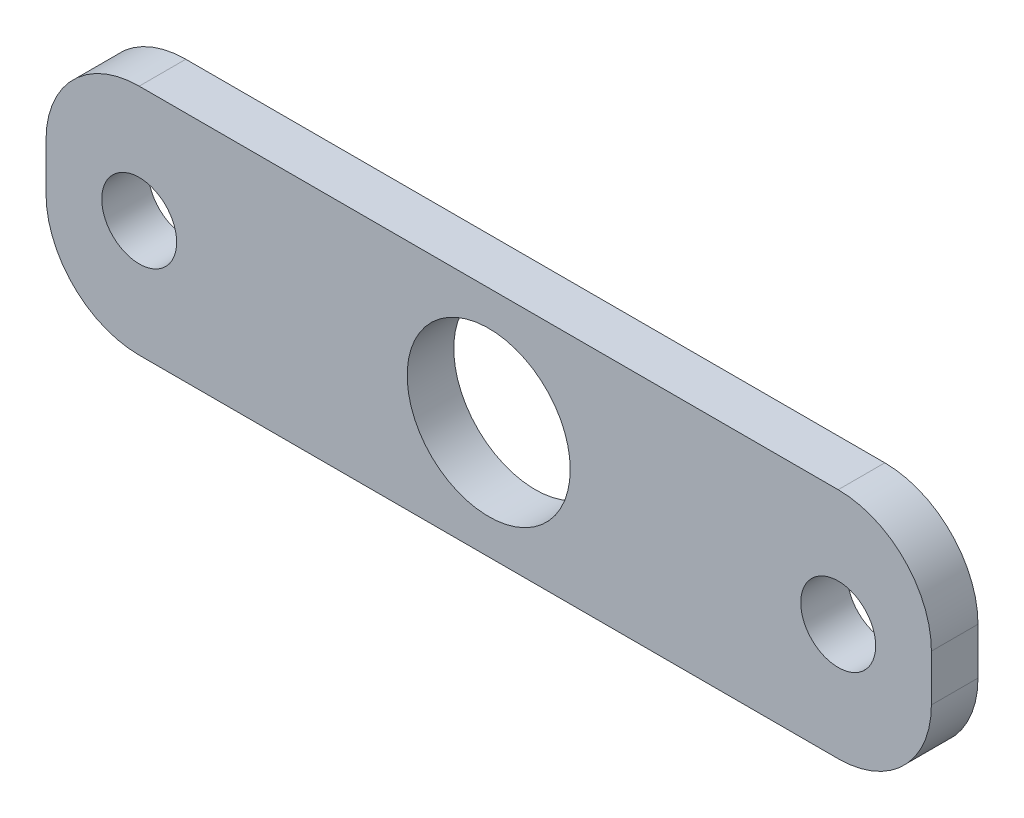
SolidWorks part; units mm, degrees
ref_plane "Front Plane" through (0, 0, 0) normal (0, 0, 1) x (1, 0, 0)
ref_plane "Top Plane" through (0, 0, 0) normal (0, 1, 0) x (1, 0, 0)
ref_plane "Right Plane" through (0, 0, 0) normal (1, 0, 0) x (0, 0, -1)
sketch "Sketch1" plane through (0, 0, 0) normal (0, 0, 1) x (1, 0, 0)
  line L0 (-23.8125, 0) -> (23.8125, 0) construction
  line L2 (-30.1625, 7.9375) -> (30.1625, 7.9375)
  line L3 (-30.1625, 7.9375) -> (-30.1625, -7.9375)
  line L4 (-30.1625, -7.9375) -> (30.1625, -7.9375)
  line L5 (30.1625, 7.9375) -> (30.1625, -7.9375)
  line L6 (-30.1625, 7.9375) -> (30.1625, -7.9375) construction
  line L7 (-30.1625, -7.9375) -> (30.1625, 7.9375) construction
  line L8 (-30.1625, 12.7) -> (30.1625, 12.7) construction
  line L9 (-30.1625, 12.7) -> (-30.1625, -12.7) construction
  line L10 (-30.1625, -12.7) -> (30.1625, -12.7) construction
  line L11 (30.1625, 12.7) -> (30.1625, -12.7) construction
  line L12 (-30.1625, 12.7) -> (30.1625, -12.7) construction
  line L13 (-30.1625, -12.7) -> (30.1625, 12.7) construction
  circle A0 centre (0, 0) radius 5.5562
  circle A1 centre (23.8125, 0) radius 2.5527
  circle A2 centre (-23.8125, 0) radius 2.5527
  circle A3 centre (0, 0) radius 6.3489 construction
  circle A4 centre (0, 0) radius 7.9364 construction
  circle A5 centre (-23.8125, 0) radius 4.1402
  circle A6 centre (23.8125, 0) radius 4.1402
  arc A8 (-1.2652, -7.8349) -> (1.2652, -7.8349) centre (0, 0) ccw
  point P0 (0, 0)
  dimension "D3" = 47.625
  dimension "D4" = 5.1054
  dimension "D5" = 11.1125
  dimension "D1" = 60.325
  dimension "D2" = 25.4
  dimension "D6" = 1.5875
  dimension "D7" = 15.875
  dimension "D9" = 1.5875
extrude "Boss-Extrude1" add sketch "Sketch1" along normal mid plane 3.175 contours A5 A0 A6 | A5 A2 | A8 A6 A0 A5 | A6 A1 | A5 A0 | A6 A0 region at (0, 7.3137, 0) region at (-27.8356, 0, 0) region at (19.7894, 0, 0)
fillet "Fillet3" radius 6.35 4 edges at (30.1625, -7.9375, 0) (-30.1625, -7.9375, 0) (30.1625, 7.9375, 0) (-30.1625, 7.9375, 0)
